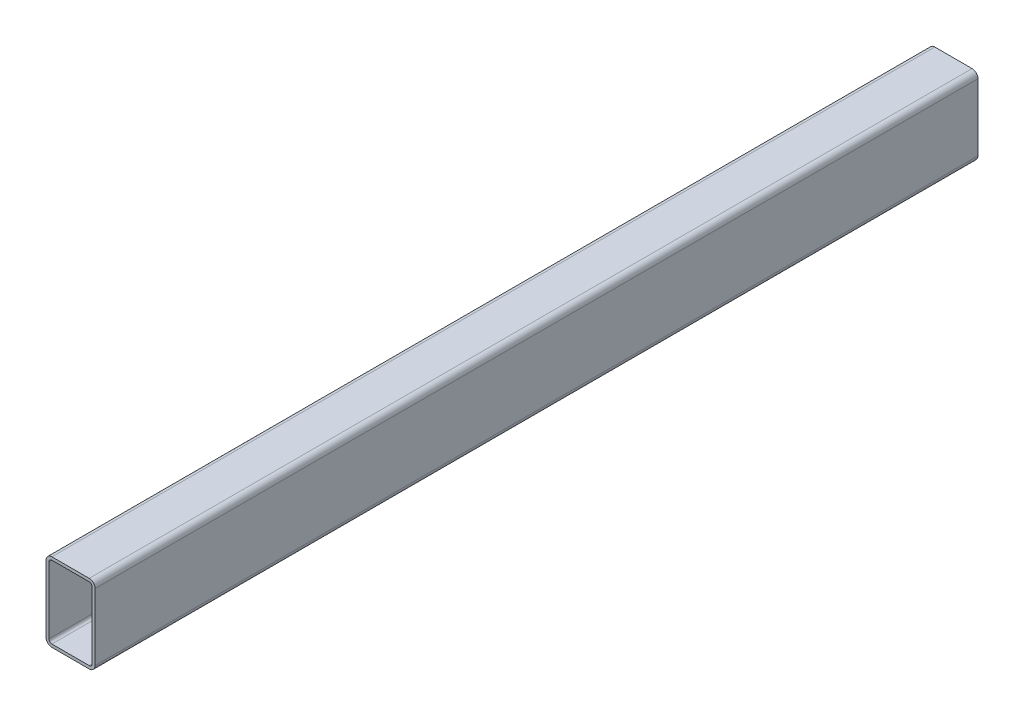
SolidWorks part; units mm, degrees
ref_plane "Front Plane" through (0, 0, 0) normal (0, 0, 1) x (1, 0, 0)
ref_plane "Top Plane" through (0, 0, 0) normal (0, 1, 0) x (1, 0, 0)
ref_plane "Right Plane" through (0, 0, 0) normal (1, 0, 0) x (0, 0, -1)
sketch "Sketch1" plane through (0, 0, 0) normal (0, 0, 1) x (1, 0, 0)
  line L0 (19, 37) -> (-19, 37)
  line L1 (19, -40) -> (-19, -40)
  line L2 (25, -34) -> (25, 34)
  line L3 (19, 40) -> (-19, 40)
  line L4 (-25, -34) -> (-25, 34)
  line L5 (25, -40) -> (-25, 40) construction
  line L6 (25, 40) -> (-25, -40) construction
  line L7 (-22, -34) -> (-22, 34)
  line L8 (19, -37) -> (-19, -37)
  line L9 (22, -34) -> (22, 34)
  arc A0 (-19, -40) -> (-25, -34) centre (-19, -34) cw
  arc A1 (19, -40) -> (25, -34) centre (19, -34) ccw
  arc A2 (25, 34) -> (19, 40) centre (19, 34) ccw
  arc A3 (-19, 40) -> (-25, 34) centre (-19, 34) ccw
  arc A4 (-19, 37) -> (-22, 34) centre (-19, 34) ccw
  arc A5 (-19, -37) -> (-22, -34) centre (-19, -34) cw
  arc A6 (19, -37) -> (22, -34) centre (19, -34) ccw
  arc A7 (22, 34) -> (19, 37) centre (19, 34) ccw
  point P0 (0, 0)
  dimension "D1" = 6
  dimension "D3" = 80
  dimension "D4" = 50
  dimension "D2" = 3
extrude "Boss-Extrude1" add sketch "Sketch1" along normal mid plane 900
equation "\"M5_tap\"=4.2mm"
equation "\"M5_clearence\"=5.5mm"
equation "\"M6_tap\"=5mm"
equation "\"M6_clearence\"=6.6mm"
equation "\"work_area_width\"=1100mm"
equation "\"work_area_depth\"=900mm"
equation "\"D3@Sketch1\"=\"steel_sides_width\""
equation "\"D4@Sketch1\"=\"steel_sides_height\""
equation "\"D1@Sketch1\"=\"steel_sides_radius\""
equation "\"D2@Sketch1\"=\"steel_sides_wall_thickness\""
equation "\"D1@Boss-Extrude1\"=\"work_area_depth\""
equation "\"steel_base_width\"=80mm"
equation "\"steel_base_height\"=50mm"
equation "\"steel_base_wall_thickness\"=3mm"
equation "\"steel_base_radius\"=6mm"
equation "\"steel_sides_width\"=80mm    'this tube is rotated so flip width/height"
equation "\"steel_sides_height\"=50mm    'this tube is rotated so flip width/height"
equation "\"steel_sides_wall_thickness\"=3mm"
equation "\"steel_sides_radius\"=6mm"
equation "\"steel_gantry_width\"=80mm    'this tube is rotated so flip width/height"
equation "\"steel_gantry_height\"=50mm    'this tube is rotated so flip width/height"
equation "\"steel_gantry_wall_thickness\"=3mm"
equation "\"steel_gantry_radius\"=6mm"
equation "\"steel_rollers_width\"=80mm"
equation "\"steel_rollers_height\"=50mm    'keep as low as possible as this increases how big plastic parts are"
equation "\"steel_rollers_wall_thickness\"=3mm"
equation "\"steel_rollers_radius\"=6mm"
equation "\"steel_zbox_width\"=80mm     'if the gantry height (rotated) is too thick, a wider zbox is necessary"
equation "\"steel_zbox_height\"=50mm    'hole patteren changes as the zbox and gantry height (rotated) changes."
equation "\"steel_zbox_wall_thickness\"=3mm"
equation "\"steel_zbox_radius\"=6mm"
equation "\"alu_zangle_width\"=80mm     'check that it doesn't interfer with the gantry"
equation "\"alu_zangle_height\"=50mm"
equation "\"alu_zangle_wall_thickness\"=10mm  'check that it doesn't interfer with the gantry"
